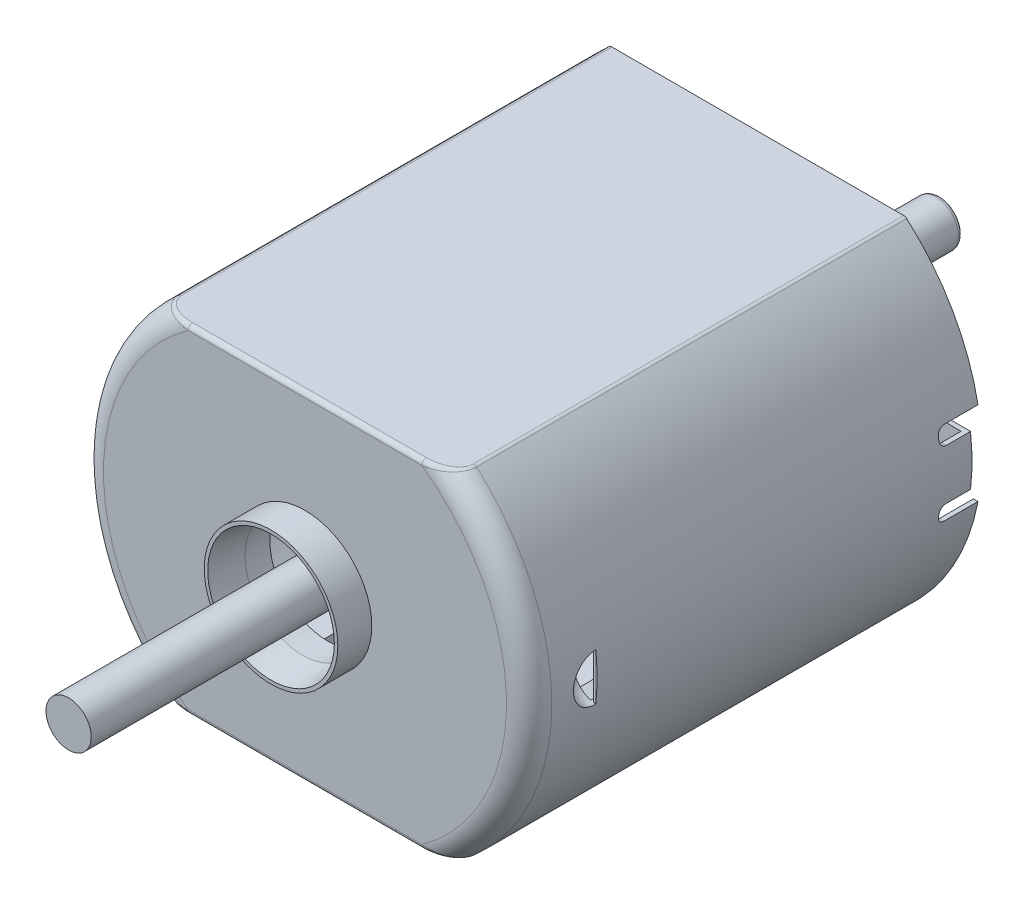
SolidWorks part; units mm, degrees
ref_plane "Front Plane" through (0, 0, 0) normal (0, 0, 1) x (1, 0, 0)
ref_plane "Top Plane" through (0, 0, 0) normal (0, 1, 0) x (1, 0, 0)
ref_plane "Right Plane" through (0, 0, 0) normal (1, 0, 0) x (0, 0, -1)
sketch "Sketch1" plane through (0, 0, 0) normal (0, 0, 1) x (1, 0, 0)
  line L1 (-6.5198, -7.45) -> (6.5198, -7.45)
  line L3 (-6.5198, 7.45) -> (6.5198, 7.45)
  arc A0 (-6.5198, 7.45) -> (-6.5198, -7.45) centre (0, 0) ccw
  arc A1 (6.5198, -7.45) -> (6.5198, 7.45) centre (0, 0) ccw
  dimension "D1" = 19.8
extrude "Boss-Extrude1" add sketch "Sketch1" along normal mid plane 20
fillet "Fillet1" radius 1 2 edges at (9.9, 0, 10) (-9.9, 0, 10)
fillet "Fillet2" radius 0.2 10 edges at (6.5198, 7.45, -0.5) (6.0891, 7.45, 9.692) (-6.5198, 7.45, -0.5) (-6.3441, 7.45, 9.4652) (-6.5198, -7.45, -0.5) (-6.0891, -7.45, 9.692) (6.5198, -7.45, -0.5) (6.3441, -7.45, 9.4652) (0, 7.45, 10) (0, -7.45, 10)
sketch "Sketch2" plane through (0, 0, 0) normal (0, 0, 1) x (1, 0, 0)
  line L1 (2.809, -7.45) -> (4.078, -6.9055)
  line L2 (2.809, -7.45) -> (4.0654, -7.45)
  line L3 (4.078, -6.9055) -> (4.078, -6.5882)
  line L4 (4.078, -6.5882) -> (2.7041, -7.1777)
  line L5 (2.7041, -7.1777) -> (2.7041, -5.1011)
  line L6 (2.7041, -5.1011) -> (4.3754, -5.1011)
  line L7 (4.3754, -5.1011) -> (4.3754, -7.317)
  line L8 (4.3754, -7.317) -> (4.0654, -7.45)
  line L9 (0, 0) -> (0, -4.7045) construction
  line L10 (-4.3754, -7.317) -> (-4.0654, -7.45)
  line L11 (-4.3754, -5.1011) -> (-4.3754, -7.317)
  line L12 (-2.7041, -5.1011) -> (-4.3754, -5.1011)
  line L13 (-2.7041, -7.1777) -> (-2.7041, -5.1011)
  line L14 (-4.078, -6.5882) -> (-2.7041, -7.1777)
  line L15 (-4.078, -6.9055) -> (-4.078, -6.5882)
  line L16 (-2.809, -7.45) -> (-4.0654, -7.45)
  line L17 (-2.809, -7.45) -> (-4.078, -6.9055)
extrude "Cut-Extrude1" cut sketch "Sketch2" against normal mid plane 7
sketch "Sketch3" plane through (0, -7.45, 0) normal (0, -1, 0) x (1, 0, 0)
  line L0 (-4.3754, -3.5) -> (-4.3754, 3.5) construction
  line L1 (-4.3754, -3.5) -> (-4.3754, 0)
  line L2 (-4.3754, -3.5) -> (-3.4372, -3.5)
  line L3 (-4.0654, -3.5) -> (-2.809, -3.5) construction
  line L4 (-3.4372, -3.5) -> (-4.3754, 0)
  line L5 (0, 0) -> (0, -4.0148) construction
  line L6 (3.4372, -3.5) -> (4.3754, 0)
  line L7 (4.3754, -3.5) -> (3.4372, -3.5)
  line L8 (4.3754, -3.5) -> (4.3754, 0)
extrude "Boss-Extrude2" add sketch "Sketch3" against normal blind 0.1
fillet "Fillet3" radius 0.2 2 edges at (3.8678, -7.35, -1.8936) (-3.8678, -7.35, -1.8936)
sketch "Sketch4" plane through (0, 0, 10) normal (0, 0, 1) x (1, 0, 0)
  circle A0 centre (0, 0) radius 2.95
  circle A1 centre (0, 0) radius 2.55
  dimension "D1" = 5.9
  dimension "D2" = 5.1
extrude "Boss-Extrude3" add sketch "Sketch4" along normal blind 1.5
chamfer "Chamfer1" distance 1.4 angle 10 1 edges at (2.55, 0, 11.5)
sketch "Sketch5" plane through (0, 0, 0) normal (1, 0, 0) x (0, 0, -1)
  line L0 (10, -7.3995) -> (10, 7.3995) construction
  line L1 (10, -1.85) -> (10, 1.85)
  line L2 (8.2, 1.4095) -> (8.2, 1.55)
  line L3 (10, -1.85) -> (8.5, -1.85)
  line L5 (10, 1.85) -> (8.5, 1.85)
  line L6 (8.2, -1.55) -> (8.2, -1.4095)
  line L9 (8.5, -1.1095) -> (9.5592, -1.1095)
  line L11 (8.5, 1.1095) -> (9.5592, 1.1095)
  line L12 (9.5592, -1.1095) -> (9.5592, 1.1095)
  line L15 (8.2867, 1.7609) -> (8.2, 1.85) construction
  arc A0 (8.2, 1.55) -> (8.5, 1.85) centre (8.5, 1.55) cw
  arc A1 (8.5, -1.85) -> (8.2, -1.55) centre (8.5, -1.55) cw
  arc A2 (8.2, 1.4095) -> (8.5, 1.1095) centre (8.5, 1.4095) ccw
  arc A3 (8.5, -1.1095) -> (8.2, -1.4095) centre (8.5, -1.4095) ccw
  point P2 (10, 0)
  point P7 (8.2, 0)
  point P19 (8.2, 1.1095)
  dimension "D3" = 0.3
  dimension "D4" = 0.3
extrude "Cut-Extrude2" cut sketch "Sketch5" against normal mid plane 23.5
sketch "Sketch6" plane through (0, 0, -10) normal (0, 0, -1) x (-1, 0, 0)
  line L0 (-6.4442, -7.25) -> (6.4442, -7.25)
  line L1 (6.4442, 7.25) -> (-6.4442, 7.25)
  line L2 (9.8376, 1.1095) -> (-9.8376, 1.1095) construction
  line L4 (-8.5539, -1.1095) -> (-8.5539, 1.1095)
  line L6 (8.5539, -1.1095) -> (8.5539, 1.1095)
  line L9 (9.6363, 1.1095) -> (8.5539, 1.1095)
  line L10 (9.8376, -1.1095) -> (-9.8376, -1.1095) construction
  line L11 (9.6363, -1.1095) -> (8.5539, -1.1095)
  line L12 (-8.5539, 1.1095) -> (-9.6363, 1.1095)
  line L15 (-8.5539, -1.1095) -> (-9.6363, -1.1095)
  arc A0 (6.4442, -7.25) -> (9.6363, -1.1095) centre (0, 0) ccw
  arc A1 (-6.4442, 7.25) -> (-9.6363, 1.1095) centre (0, 0) ccw
  arc A2 (9.6363, 1.1095) -> (6.4442, 7.25) centre (0, 0) ccw
  arc A3 (-9.6363, -1.1095) -> (-6.4442, -7.25) centre (0, 0) ccw
extrude "Cut-Extrude3" cut sketch "Sketch6" against normal blind 5.5
sketch "Sketch7" plane through (0, 0, -4.5) normal (0, 0, -1) x (-1, 0, 0)
  line L2 (2.7041, -7.1777) -> (2.7041, -7.25)
  line L3 (-2.7041, -7.1777) -> (-2.7041, -7.25)
  line L4 (4.3754, -7.25) -> (6.4442, -7.25)
  line L5 (-2.7041, -7.25) -> (2.7041, -7.25)
  line L6 (-8.5539, -1.1095) -> (-9.6363, -1.1095) construction
  line L7 (-8.5539, 1.1095) -> (-8.5539, -1.1095) construction
  line L8 (6.4442, 7.25) -> (-6.4442, 7.25)
  line L9 (-9.6363, 1.1095) -> (-8.5539, 1.1095)
  line L10 (-8.5539, 1.1095) -> (-8.5539, -1.1095)
  line L11 (-8.5539, -1.1095) -> (-9.6363, -1.1095)
  line L12 (-6.4442, -7.25) -> (6.4442, -7.25)
  line L13 (9.6363, -1.1095) -> (8.5539, -1.1095)
  line L14 (8.5539, -1.1095) -> (8.5539, 1.1095)
  line L15 (8.5539, 1.1095) -> (9.6363, 1.1095)
  line L16 (6.4442, 7.25) -> (-6.4442, 7.25)
  line L17 (-9.6363, 1.1095) -> (-8.5539, 1.1095) construction
  line L18 (-8.5539, -1.1095) -> (-9.6363, -1.1095)
  line L19 (-8.5539, 1.1095) -> (-8.5539, -1.1095)
  line L20 (-6.4442, -7.25) -> (-4.3754, -7.25)
  line L21 (-9.6363, 1.1095) -> (-8.5539, 1.1095)
  line L22 (9.6363, -1.1095) -> (8.5539, -1.1095) construction
  line L23 (8.5539, -1.1095) -> (8.5539, 1.1095) construction
  line L24 (4.3754, -7.317) -> (4.3754, -5.1011)
  line L25 (4.3754, -5.1011) -> (2.7041, -5.1011)
  line L26 (2.7041, -5.1011) -> (2.7041, -7.1777)
  line L27 (2.7041, -7.1777) -> (4.078, -6.5882)
  line L28 (4.078, -6.5882) -> (4.078, -6.9055)
  line L29 (4.078, -6.9055) -> (2.809, -7.45)
  line L30 (2.809, -7.45) -> (4.0654, -7.45)
  line L31 (4.0654, -7.45) -> (4.3754, -7.317)
  line L32 (4.3754, -7.25) -> (4.3754, -5.1011)
  line L33 (4.3754, -5.1011) -> (2.7041, -5.1011)
  line L34 (2.7041, -5.1011) -> (2.7041, -7.1777)
  line L35 (8.5539, 1.1095) -> (9.6363, 1.1095) construction
  line L36 (9.6363, -1.1095) -> (8.5539, -1.1095)
  line L37 (8.5539, -1.1095) -> (8.5539, 1.1095)
  line L38 (8.5539, 1.1095) -> (9.6363, 1.1095)
  line L40 (-4.0654, -7.45) -> (-2.809, -7.45)
  line L41 (-2.809, -7.45) -> (-4.078, -6.9055)
  line L42 (-4.078, -6.9055) -> (-4.078, -6.5882)
  line L43 (-4.078, -6.5882) -> (-2.7041, -7.1777)
  line L44 (-2.7041, -7.1777) -> (-2.7041, -5.1011)
  line L45 (-2.7041, -5.1011) -> (-4.3754, -5.1011)
  line L46 (-4.3754, -5.1011) -> (-4.3754, -7.317)
  line L47 (-4.3754, -7.317) -> (-4.0654, -7.45)
  line L52 (-2.7041, -7.1777) -> (-2.7041, -5.1011)
  line L53 (-2.7041, -5.1011) -> (-4.3754, -5.1011)
  line L54 (-4.3754, -5.1011) -> (-4.3754, -7.25)
  arc A4 (9.6363, 1.1095) -> (6.4442, 7.25) centre (0, 0) ccw
  arc A5 (-6.4442, 7.25) -> (-9.6363, 1.1095) centre (0, 0) ccw
  arc A6 (-9.6363, -1.1095) -> (-6.4442, -7.25) centre (0, 0) ccw
  arc A7 (6.4442, -7.25) -> (9.6363, -1.1095) centre (0, 0) ccw
  arc A8 (9.6363, 1.1095) -> (6.4442, 7.25) centre (0, 0) ccw
  arc A9 (-6.4442, 7.25) -> (-9.6363, 1.1095) centre (0, 0) ccw
  arc A10 (-9.6363, -1.1095) -> (-6.4442, -7.25) centre (0, 0) ccw
  arc A11 (6.4442, -7.25) -> (9.6363, -1.1095) centre (0, 0) ccw
  dimension "D1" = 0
  dimension "D2" = 0
  dimension "D3" = 0
extrude "Cut-Extrude4" cut sketch "Sketch7" against normal blind 13.5
sketch "Sketch8" plane through (0, 0, 10) normal (0, 0, 1) x (1, 0, 0)
  circle A1 centre (0, 0) radius 2.55
  circle A2 centre (0, 0) radius 2.55
  dimension "D1" = 0
extrude "Cut-Extrude5" cut sketch "Sketch8" against normal blind 13.5
sketch "Sketch10" plane through (0, 0, 0) normal (1, 0, 0) x (0, 0, -1)
  line L0 (9.3539, -1.1095) -> (9.3539, 1.1095)
  line L1 (-3.2907, -1.1095) -> (-3.2907, 1.1095)
  line L4 (-9, -1.1095) -> (9.5592, -1.1095)
  line L5 (-9, 1.1095) -> (-9, -1.1095)
  line L6 (9.5592, 1.1095) -> (-9, 1.1095)
  line L7 (9.5592, -1.1095) -> (9.5592, 1.1095)
  line L8 (-3.2907, -1.1095) -> (9.3539, -1.1095)
  line L10 (9.3539, 1.1095) -> (-3.2907, 1.1095)
  dimension "D1" = 0
extrude "Cut-Extrude6" cut sketch "Sketch10" against normal mid plane 19.25
ref_plane "Plane1" through (0, 0, 7) normal (0, 0, 1) x (1, 0, 0)
sketch "Sketch11" plane through (0, 0, 7) normal (0, 0, 1) x (1, 0, 0)
  line L0 (0, 0) -> (0, 4.8244) construction
  line L1 (9.9, -1.0407) -> (9.9, 1.0407)
  line L2 (-9.9, -1.0407) -> (-9.9, 1.0407) construction
  arc A0 (-9.9, 1.0407) -> (-9.9, -1.0407) centre (-9.9, 0) cw construction
  arc A2 (9.9, 1.0407) -> (9.9, -1.0407) centre (9.9, 0) ccw
revolve "Cut-Revolve1" cut sketch "Sketch11" angle 180 about L1
sketch "Sketch13" plane through (0, 0, 7) normal (0, 0, 1) x (1, 0, 0)
  line L0 (0, 0) -> (0, 8.1104) construction
  line L1 (9.9, -1.0407) -> (9.9, 1.0407)
  line L2 (9.9, -1.0407) -> (9.9, 1.0407) construction
  line L3 (-9.9, -1.0407) -> (-9.9, 1.0407)
  arc A0 (-9.9, 1.0407) -> (-9.9, -1.0407) centre (-9.9, 0) cw
  arc A1 (9.9, 1.0407) -> (9.9, -1.0407) centre (9.9, 0) ccw
  arc A2 (9.9, 1.0407) -> (9.9, -1.0407) centre (9.9, 0) ccw construction
  dimension "D1" = 0
revolve "Cut-Revolve2" cut sketch "Sketch13" angle 180 about L3
sketch "Sketch15" plane through (0, 0, 3.2907) normal (0, 0, -1) x (-1, 0, 0)
  line L4 (8.5539, -1.1095) -> (9.625, -1.1095)
  line L5 (9.625, -1.1095) -> (9.625, 1.1095)
  line L6 (9.625, 1.1095) -> (8.5539, 1.1095)
  line L7 (8.5539, 1.1095) -> (8.5539, -1.1095)
  line L8 (8.5539, -1.1095) -> (9.625, -1.1095)
  line L9 (9.625, -1.1095) -> (9.625, 1.1095)
  line L10 (9.625, 1.1095) -> (8.5539, 1.1095)
  line L11 (8.5539, 1.1095) -> (8.5539, -1.1095)
  line L12 (-8.5539, 1.1095) -> (-9.625, 1.1095)
  line L13 (-9.625, 1.1095) -> (-9.625, -1.1095)
  line L14 (-9.625, -1.1095) -> (-8.5539, -1.1095)
  line L15 (-8.5539, -1.1095) -> (-8.5539, 1.1095)
  line L16 (-8.5539, 1.1095) -> (-9.625, 1.1095)
  line L17 (-9.625, 1.1095) -> (-9.625, -1.1095)
  line L18 (-9.625, -1.1095) -> (-8.5539, -1.1095)
  line L19 (-8.5539, -1.1095) -> (-8.5539, 1.1095)
  dimension "D1" = 0
  dimension "D2" = 0
extrude "Cut-Extrude7" cut sketch "Sketch15" against normal up to surface (3.7093 mm away) up to face at (-9.3796, 0, 7)
fillet "Fillet4" radius 0.2 2 edges at (9.625, 0, 7) (-9.625, 0, 7)
sketch "Sketch16" plane through (0, 0, -9.5592) normal (0, 0, -1) x (-1, 0, 0)
  circle A0 centre (0, 0) radius 1 construction
  circle A1 centre (0, 0) radius 1
extrude "Boss-Extrude4" add sketch "Sketch16" along normal blind 8.5 separate body
fillet "Fillet5" radius 0.2 1 edges at (-1, 0, -18.0592)
sketch "Sketch17" plane through (0, 0, -9.5592) normal (0, 0, 1) x (1, 0, 0)
  circle A1 centre (0, 0) radius 1
  circle A2 centre (0, 0) radius 1
  dimension "D1" = 0
extrude "Boss-Extrude5" add sketch "Sketch17" along normal blind 30
